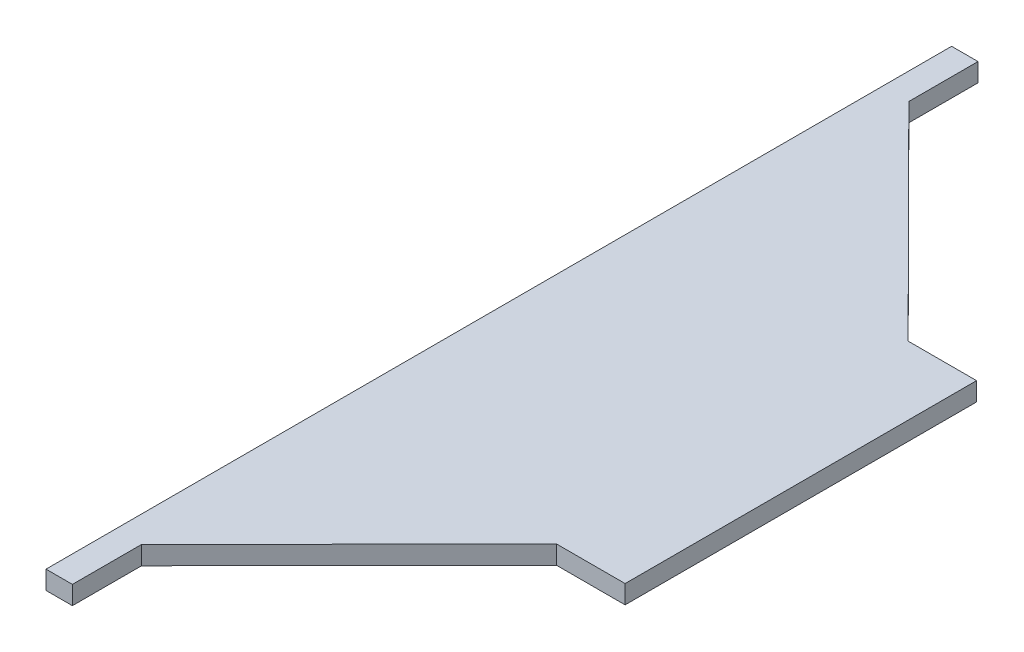
SolidWorks part; units mm, degrees
ref_plane "Front Plane" through (0, 0, 0) normal (0, 0, 1) x (1, 0, 0)
ref_plane "Top Plane" through (0, 0, 0) normal (0, 1, 0) x (1, 0, 0)
ref_plane "Right Plane" through (0, 0, 0) normal (1, 0, 0) x (0, 0, -1)
sketch "Croquis1" plane through (0, 0, 0) normal (0, 1, 0) x (1, 0, 0)
  line L0 (0, 0) -> (0, -102.91)
  line L1 (0, -102.91) -> (3, -102.91)
  line L2 (3, -102.91) -> (3, -95.05)
  line L3 (3, -95.05) -> (26.5427, -71.425)
  line L4 (26.5427, -71.425) -> (34.3227, -71.425)
  line L5 (34.3227, -71.425) -> (34.3227, -31.485)
  line L6 (34.3227, -31.485) -> (26.5427, -31.485)
  line L7 (26.5427, -31.485) -> (3, -7.86)
  line L8 (3, -7.86) -> (3, 0)
  line L9 (3, 0) -> (0, 0)
  point P3 (0, 0)
  point P12 (34.3227, -51.455)
  point P13 (0, -51.455)
  dimension "D1" = 3
  dimension "D2" = 102.91
  dimension "D3" = 7.86
  dimension "D4" = 7.86
  dimension "D5" = 7.78
  dimension "D6" = 39.94
  dimension "D7" = 135.1
extrude "Saliente-Extruir1" add sketch "Croquis1" along normal blind 2.1
